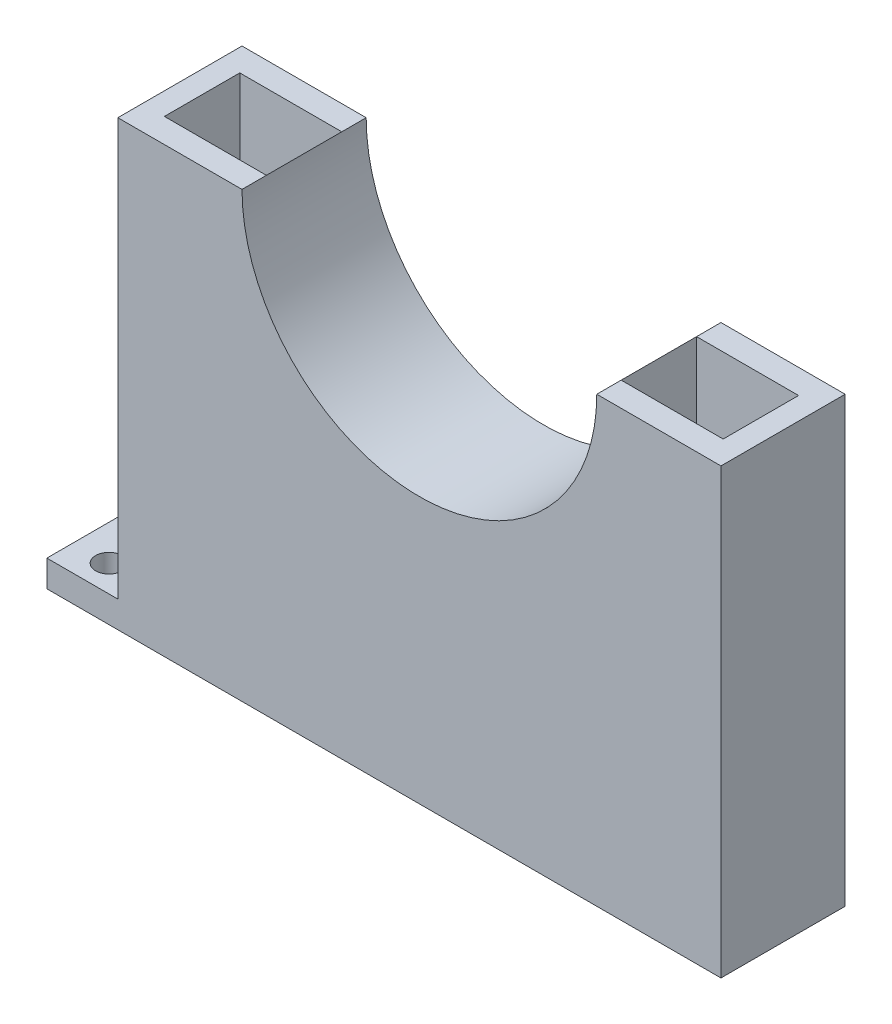
SolidWorks part; units mm, degrees
ref_plane "Front Plane" through (0, 0, 0) normal (0, 0, 1) x (1, 0, 0)
ref_plane "Top Plane" through (0, 0, 0) normal (0, 1, 0) x (1, 0, 0)
ref_plane "Right Plane" through (0, 0, 0) normal (1, 0, 0) x (0, 0, -1)
sketch "Sketch1" plane through (0, 0, 0) normal (0, 0, 1) x (1, 0, 0)
  line L0 (0, 0) -> (0, 3)
  line L1 (0, 3) -> (8, 3)
  line L2 (0, 0) -> (76, 0)
  line L3 (76, 0) -> (76, 50)
  line L4 (8, 3) -> (8, 50)
  line L5 (8, 50) -> (22, 50)
  line L6 (76, 50) -> (62, 50)
  arc A1 (62, 50) -> (22, 50) centre (42, 50) cw
  dimension "D1" = 14
  dimension "D2" = 20
  dimension "D3" = 3
  dimension "D4" = 50
  dimension "D5" = 8
extrude "Boss-Extrude1" add sketch "Sketch1" along normal blind 14
sketch "Sketch2" plane through (0, 0, 0) normal (0, -1, 0) x (1, 0, 0)
  line L0 (42, 14) -> (42, 0) construction
  line L1 (0, 14) -> (76, 14) construction
  line L2 (0, 0) -> (76, 0) construction
  line L3 (62, 14) -> (22, 14) construction
  line L4 (73.5, 11.25) -> (62, 11.25)
  line L5 (62, 11.25) -> (62, 2.75)
  line L6 (62, 2.75) -> (73.5, 2.75)
  line L7 (73.5, 2.75) -> (73.5, 11.25)
  line L10 (76, 14) -> (76, 0) construction
  line L11 (22, 2.75) -> (10.5, 2.75)
  line L12 (22, 11.25) -> (22, 2.75)
  line L13 (10.5, 11.25) -> (22, 11.25)
  line L14 (10.5, 2.75) -> (10.5, 11.25)
  point P14 (76, 7)
  point P15 (73.5, 7)
  dimension "D1" = 11.5
  dimension "D2" = 8.5
  dimension "D3" = 2.5
extrude "Cut-Extrude1" cut sketch "Sketch2" against normal up to surface (50 mm away) up to face at (15, 50, 7)
sketch "Sketch3" plane through (0, 3, 0) normal (0, 1, 0) x (1, 0, 0)
  line L0 (4, -3) -> (4, -11) construction
  line L1 (0, -14) -> (0, 0) construction
  line L4 (8, -14) -> (0, -14) construction
  circle A0 centre (4, -3) radius 1.5
  circle A1 centre (4, -11) radius 1.5
  point P4 (0, 0)
  point P7 (4, -14)
  point P10 (0, -7)
  point P11 (4, -7)
  dimension "D1" = 3
  dimension "D2" = 3
  dimension "D3" = 8
extrude "screw holes" cut sketch "Sketch3" against normal up to surface (3 mm away) up to face at (67.75, 0, 7)
